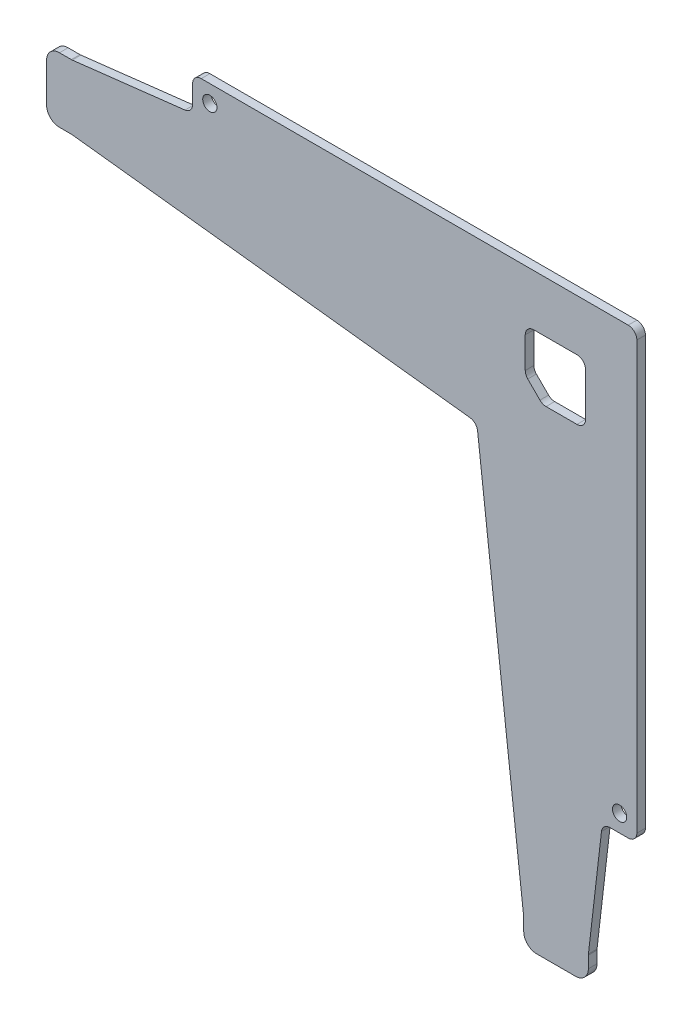
SolidWorks part; units mm, degrees
ref_plane "Front Plane" through (0, 0, 0) normal (0, 0, 1) x (1, 0, 0)
ref_plane "Top Plane" through (0, 0, 0) normal (0, 1, 0) x (1, 0, 0)
ref_plane "Right Plane" through (0, 0, 0) normal (1, 0, 0) x (0, 0, -1)
sketch "Sketch1" plane through (0, 0, 0) normal (0, 0, 1) x (1, 0, 0)
  line L0 (-136, -10.25) -> (-136, -25.25)
  line L1 (-25.25, -136) -> (-10.25, -136)
  line L2 (-136, -10.25) -> (-145.5, -10.25) construction
  line L3 (-136, -25.25) -> (-130.2599, -25.25)
  line L4 (-25.25, -136) -> (-25.25, -145.5) construction
  line L5 (-10.25, -136) -> (-10.25, -130.2599)
  line L23 (-12.75, -142) -> (-12.75, -145.5)
  line L24 (-12.75, -145.5) -> (-10.25, -145.5)
  line L25 (-10.25, -145.5) -> (-10.25, -130.2599)
  line L26 (-10.2367, -130.0296) -> (-7.2051, -103.8749)
  line L27 (-5.2184, -102.1052) -> (-1, -102.1052)
  line L28 (1, -100.1052) -> (1, -1)
  line L29 (-1, 1) -> (-100.1052, 1)
  line L30 (-102.1052, -1) -> (-102.1052, -5.2184)
  line L31 (-103.8749, -7.2051) -> (-130.0296, -10.2367)
  line L32 (-130.2599, -10.25) -> (-145.5, -10.25)
  line L33 (-145.5, -10.25) -> (-145.5, -12.75)
  line L34 (-145.5, -12.75) -> (-142, -12.75)
  line L35 (-140, -14.75) -> (-140, -20.75)
  line L36 (-142, -22.75) -> (-145.5, -22.75)
  line L37 (-145.5, -22.75) -> (-145.5, -25.25)
  line L38 (-145.5, -25.25) -> (-130.2599, -25.25)
  line L39 (-130.0296, -25.2633) -> (-37.7193, -35.9629)
  line L41 (-35.9629, -37.7193) -> (-25.2633, -130.0296)
  line L42 (-25.25, -130.2599) -> (-25.25, -145.5)
  line L43 (-25.25, -145.5) -> (-22.75, -145.5)
  line L44 (-22.75, -145.5) -> (-22.75, -142)
  line L45 (-20.75, -140) -> (-14.75, -140)
  line L46 (-12.75, -142) -> (-12.75, -145.5) construction
  line L47 (-12.75, -145.5) -> (-10.25, -145.5) construction
  line L48 (-10.25, -145.5) -> (-10.25, -136) construction
  line L49 (-10.2367, -130.0296) -> (-7.2051, -103.8749)
  line L50 (-5.2184, -102.1052) -> (-1, -102.1052)
  line L51 (1, -100.1052) -> (1, -1)
  line L52 (-1, 1) -> (-100.1052, 1)
  line L53 (-102.1052, -1) -> (-102.1052, -5.2184)
  line L54 (-103.8749, -7.2051) -> (-130.0296, -10.2367)
  line L55 (-130.2599, -10.25) -> (-136, -10.25)
  line L56 (-145.5, -10.25) -> (-145.5, -12.75) construction
  line L57 (-145.5, -12.75) -> (-142, -12.75) construction
  line L58 (-140, -14.75) -> (-140, -20.75) construction
  line L59 (-142, -22.75) -> (-145.5, -22.75) construction
  line L60 (-145.5, -22.75) -> (-145.5, -25.25) construction
  line L61 (-145.5, -25.25) -> (-136, -25.25) construction
  line L62 (-130.0296, -25.2633) -> (-37.7193, -35.9629)
  line L64 (-35.9629, -37.7193) -> (-25.2633, -130.0296)
  line L65 (-25.25, -130.2599) -> (-25.25, -136)
  line L66 (-25.25, -145.5) -> (-22.75, -145.5) construction
  line L67 (-22.75, -145.5) -> (-22.75, -142) construction
  line L68 (-20.75, -140) -> (-14.75, -140) construction
  arc A15 (-10.2367, -130.0296) -> (-10.25, -130.2599) centre (-8.25, -130.2599) ccw
  arc A16 (-5.2184, -102.1052) -> (-7.2051, -103.8749) centre (-5.2184, -104.1052) ccw
  arc A17 (-1, -102.1052) -> (1, -100.1052) centre (-1, -100.1052) ccw
  arc A18 (1, -1) -> (-1, 1) centre (-1, -1) ccw
  arc A19 (-100.1052, 1) -> (-102.1052, -1) centre (-100.1052, -1) ccw
  arc A20 (-103.8749, -7.2051) -> (-102.1052, -5.2184) centre (-104.1052, -5.2184) ccw
  arc A21 (-130.2599, -10.25) -> (-130.0296, -10.2367) centre (-130.2599, -8.25) ccw
  arc A22 (-140, -14.75) -> (-142, -12.75) centre (-142, -14.75) ccw
  arc A23 (-142, -22.75) -> (-140, -20.75) centre (-142, -20.75) ccw
  arc A24 (-130.0296, -25.2633) -> (-130.2599, -25.25) centre (-130.2599, -27.25) ccw
  arc A25 (-35.9629, -37.7193) -> (-37.7193, -35.9629) centre (-37.9496, -37.9496) ccw
  arc A26 (-35.9629, -37.7193) -> (-37.7193, -35.9629) centre (-37.9496, -37.9496) ccw
  arc A27 (-25.25, -130.2599) -> (-25.2633, -130.0296) centre (-27.25, -130.2599) ccw
  arc A28 (-20.75, -140) -> (-22.75, -142) centre (-20.75, -142) ccw
  arc A29 (-12.75, -142) -> (-14.75, -140) centre (-14.75, -142) ccw
  arc A30 (-10.2367, -130.0296) -> (-10.25, -130.2599) centre (-8.25, -130.2599) ccw
  arc A31 (-5.2184, -102.1052) -> (-7.2051, -103.8749) centre (-5.2184, -104.1052) ccw
  arc A32 (-1, -102.1052) -> (1, -100.1052) centre (-1, -100.1052) ccw
  arc A33 (1, -1) -> (-1, 1) centre (-1, -1) ccw
  arc A34 (-100.1052, 1) -> (-102.1052, -1) centre (-100.1052, -1) ccw
  arc A35 (-103.8749, -7.2051) -> (-102.1052, -5.2184) centre (-104.1052, -5.2184) ccw
  arc A36 (-130.2599, -10.25) -> (-130.0296, -10.2367) centre (-130.2599, -8.25) ccw
  arc A37 (-140, -14.75) -> (-142, -12.75) centre (-142, -14.75) ccw construction
  arc A38 (-142, -22.75) -> (-140, -20.75) centre (-142, -20.75) ccw construction
  arc A39 (-130.0296, -25.2633) -> (-130.2599, -25.25) centre (-130.2599, -27.25) ccw
  arc A42 (-25.25, -130.2599) -> (-25.2633, -130.0296) centre (-27.25, -130.2599) ccw
  arc A43 (-20.75, -140) -> (-22.75, -142) centre (-20.75, -142) ccw construction
  arc A44 (-12.75, -142) -> (-14.75, -140) centre (-14.75, -142) ccw construction
  dimension "D2" = 4
  dimension "D3" = 4
  dimension "D1" = 0
sketch "Sketch2" plane through (0, 0, 0) normal (0, 0, 1) x (1, 0, 0)
  circle A0 centre (-98.1052, -3) radius 1.65 construction
  circle A1 centre (-3, -98.1052) radius 1.65 construction
  circle A2 centre (-98.1052, -3) radius 1.65
  circle A3 centre (-3, -98.1052) radius 1.65
sketch "Sketch4" plane through (0, 0, 0) normal (0, 0, 1) x (1, 0, 0)
  line L0 (-24.8997, -12.8997) -> (-24.8997, -20.0712) construction
  line L1 (-12.8997, -10.8997) -> (-22.8997, -10.8997) construction
  line L2 (-10.8997, -22.8997) -> (-10.8997, -12.8997) construction
  line L3 (-20.0712, -24.8997) -> (-12.8997, -24.8997) construction
  line L4 (-24.8997, -12.8997) -> (-24.8997, -20.0712)
  line L5 (-12.8997, -10.8997) -> (-22.8997, -10.8997)
  line L6 (-10.8997, -22.8997) -> (-10.8997, -12.8997)
  line L7 (-20.0712, -24.8997) -> (-12.8997, -24.8997)
  line L8 (-21.4854, -24.3139) -> (-24.3139, -21.4854) construction
  line L9 (-21.4854, -24.3139) -> (-24.3139, -21.4854)
  arc A0 (-24.8997, -20.0712) -> (-24.3139, -21.4854) centre (-22.8997, -20.0712) ccw construction
  arc A1 (-21.4854, -24.3139) -> (-20.0712, -24.8997) centre (-20.0712, -22.8997) ccw construction
  arc A2 (-22.8997, -10.8997) -> (-24.8997, -12.8997) centre (-22.8997, -12.8997) ccw construction
  arc A3 (-10.8997, -12.8997) -> (-12.8997, -10.8997) centre (-12.8997, -12.8997) ccw construction
  arc A4 (-12.8997, -24.8997) -> (-10.8997, -22.8997) centre (-12.8997, -22.8997) ccw construction
  arc A5 (-24.8997, -20.0712) -> (-24.3139, -21.4854) centre (-22.8997, -20.0712) ccw
  arc A6 (-22.8997, -10.8997) -> (-24.8997, -12.8997) centre (-22.8997, -12.8997) ccw
  arc A7 (-10.8997, -12.8997) -> (-12.8997, -10.8997) centre (-12.8997, -12.8997) ccw
  arc A8 (-12.8997, -24.8997) -> (-10.8997, -22.8997) centre (-12.8997, -22.8997) ccw
  arc A9 (-21.4854, -24.3139) -> (-20.0712, -24.8997) centre (-20.0712, -22.8997) ccw
extrude "Boss-Extrude1" add sketch "Sketch1" along normal blind 2
extrude "Cut-Extrude2" cut sketch "Sketch4" along normal through all
sketch "Sketch5" plane through (0, 0, 0) normal (0, 0, 1) x (1, 0, 0)
  line L0 (-31.5222, -35.2107) -> (-20.7903, -127.8)
  line L1 (-20.7903, -127.8) -> (-14.7097, -127.8)
  line L2 (-14.7097, -127.8) -> (-3.7, -32.8141)
  line L3 (-3.7, -32.8141) -> (-3.7, -3.7)
  line L4 (-3.7, -3.7) -> (-32.8141, -3.7)
  line L5 (-32.8141, -3.7) -> (-127.8, -14.7097)
  line L6 (-127.8, -14.7097) -> (-127.8, -20.7903)
  line L7 (-127.8, -20.7903) -> (-35.2107, -31.5222)
  line L8 (-33.7076, -35.464) -> (-22.9551, -128.2303)
  line L9 (-20.9684, -130) -> (-14.5316, -130)
  line L10 (-12.5449, -128.2303) -> (-1.5133, -33.0559)
  line L11 (-1.5, -32.8257) -> (-1.5, -3.5)
  line L12 (-3.5, -1.5) -> (-32.8257, -1.5)
  line L13 (-33.0559, -1.5133) -> (-128.2303, -12.5449)
  line L14 (-130, -14.5316) -> (-130, -20.9684)
  line L15 (-128.2303, -22.9551) -> (-35.464, -33.7076)
  line L16 (-33.7076, -35.464) -> (-22.9551, -128.2303) construction
  line L17 (-20.9684, -130) -> (-14.5316, -130) construction
  line L18 (-12.5449, -128.2303) -> (-1.5133, -33.0559) construction
  line L19 (-1.5, -32.8257) -> (-1.5, -3.5) construction
  line L20 (-3.5, -1.5) -> (-32.8257, -1.5) construction
  line L21 (-33.0559, -1.5133) -> (-128.2303, -12.5449) construction
  line L22 (-130, -14.5316) -> (-130, -20.9684) construction
  line L23 (-128.2303, -22.9551) -> (-35.464, -33.7076) construction
  line L24 (-12.6442, -128.2188) -> (-1.6126, -33.0444)
  line L25 (-1.6, -32.8257) -> (-1.6, -3.5)
  line L26 (-3.5, -1.6) -> (-32.8257, -1.6)
  line L27 (-33.0444, -1.6126) -> (-128.2188, -12.6442)
  line L28 (-129.9, -14.5316) -> (-129.9, -20.9684)
  line L29 (-128.2188, -22.8558) -> (-35.4525, -33.6082)
  line L30 (-33.6082, -35.4525) -> (-22.8558, -128.2188)
  line L31 (-20.9684, -129.9) -> (-14.5316, -129.9)
  arc A0 (-20.7903, -127.8) -> (-20.7903, -127.8) centre (-20.7903, -127.8) ccw
  arc A1 (-14.7097, -127.8) -> (-14.7097, -127.8) centre (-14.7097, -127.8) ccw
  arc A2 (-3.7, -32.8141) -> (-3.7, -32.8141) centre (-3.7, -32.8141) ccw
  arc A3 (-3.7, -3.7) -> (-3.7, -3.7) centre (-3.7, -3.7) ccw
  arc A4 (-32.8141, -3.7) -> (-32.8141, -3.7) centre (-32.8141, -3.7) ccw
  arc A5 (-127.8, -14.7097) -> (-127.8, -14.7097) centre (-127.8, -14.7097) ccw
  arc A6 (-127.8, -20.7903) -> (-127.8, -20.7903) centre (-127.8, -20.7903) ccw
  arc A7 (-31.5222, -35.2107) -> (-35.2107, -31.5222) centre (-35.6943, -35.6943) ccw
  arc A8 (-22.9551, -128.2303) -> (-20.9684, -130) centre (-20.9684, -128) ccw
  arc A9 (-14.5316, -130) -> (-12.5449, -128.2303) centre (-14.5316, -128) ccw
  arc A10 (-1.5133, -33.0559) -> (-1.5, -32.8257) centre (-3.5, -32.8257) ccw
  arc A11 (-1.5, -3.5) -> (-3.5, -1.5) centre (-3.5, -3.5) ccw
  arc A12 (-32.8257, -1.5) -> (-33.0559, -1.5133) centre (-32.8257, -3.5) ccw
  arc A13 (-128.2303, -12.5449) -> (-130, -14.5316) centre (-128, -14.5316) ccw
  arc A14 (-130, -20.9684) -> (-128.2303, -22.9551) centre (-128, -20.9684) ccw
  arc A15 (-33.7076, -35.464) -> (-35.464, -33.7076) centre (-35.6943, -35.6943) ccw
  arc A16 (-22.9551, -128.2303) -> (-20.9684, -130) centre (-20.9684, -128) ccw construction
  arc A17 (-14.5316, -130) -> (-12.5449, -128.2303) centre (-14.5316, -128) ccw construction
  arc A18 (-1.5133, -33.0559) -> (-1.5, -32.8257) centre (-3.5, -32.8257) ccw construction
  arc A19 (-1.5, -3.5) -> (-3.5, -1.5) centre (-3.5, -3.5) ccw construction
  arc A20 (-32.8257, -1.5) -> (-33.0559, -1.5133) centre (-32.8257, -3.5) ccw construction
  arc A21 (-128.2303, -12.5449) -> (-130, -14.5316) centre (-128, -14.5316) ccw construction
  arc A22 (-130, -20.9684) -> (-128.2303, -22.9551) centre (-128, -20.9684) ccw construction
  arc A23 (-33.7076, -35.464) -> (-35.464, -33.7076) centre (-35.6943, -35.6943) ccw construction
  arc A24 (-1.6126, -33.0444) -> (-1.6, -32.8257) centre (-3.5, -32.8257) ccw
  arc A25 (-1.6, -3.5) -> (-3.5, -1.6) centre (-3.5, -3.5) ccw
  arc A26 (-32.8257, -1.6) -> (-33.0444, -1.6126) centre (-32.8257, -3.5) ccw
  arc A27 (-128.2188, -12.6442) -> (-129.9, -14.5316) centre (-128, -14.5316) ccw
  arc A28 (-129.9, -20.9684) -> (-128.2188, -22.8558) centre (-128, -20.9684) ccw
  arc A29 (-33.6082, -35.4525) -> (-35.4525, -33.6082) centre (-35.6943, -35.6943) ccw
  arc A30 (-22.8558, -128.2188) -> (-20.9684, -129.9) centre (-20.9684, -128) ccw
  arc A31 (-14.5316, -129.9) -> (-12.6442, -128.2188) centre (-14.5316, -128) ccw
  dimension "D1" = 0
  dimension "D2" = 2.2
  dimension "D3" = 0.1
extrude "Boss-Extrude2" add sketch "Sketch5" against normal blind 2.4
chamfer "Chamfer1" distance 2.4 angle 45 9 edges at (-81.5053, -26.1562, 0) (-32.7244, -32.7244, 0) (-127.8, -17.75, 0) (-80.3071, -9.2049, 0) (-18.2571, -3.7, 0) (-3.7, -18.2571, 0) (-9.2049, -80.3071, 0) (-17.75, -127.8, 0) (-26.1562, -81.5053, 0)
extrude "Cut-Extrude3" cut sketch "Sketch2" along normal through all
fillet "Fillet1" radius 3 4 edges at (-25.25, -136, 1) (-10.25, -136, 1) (-136, -10.25, 1) (-136, -25.25, 1)
